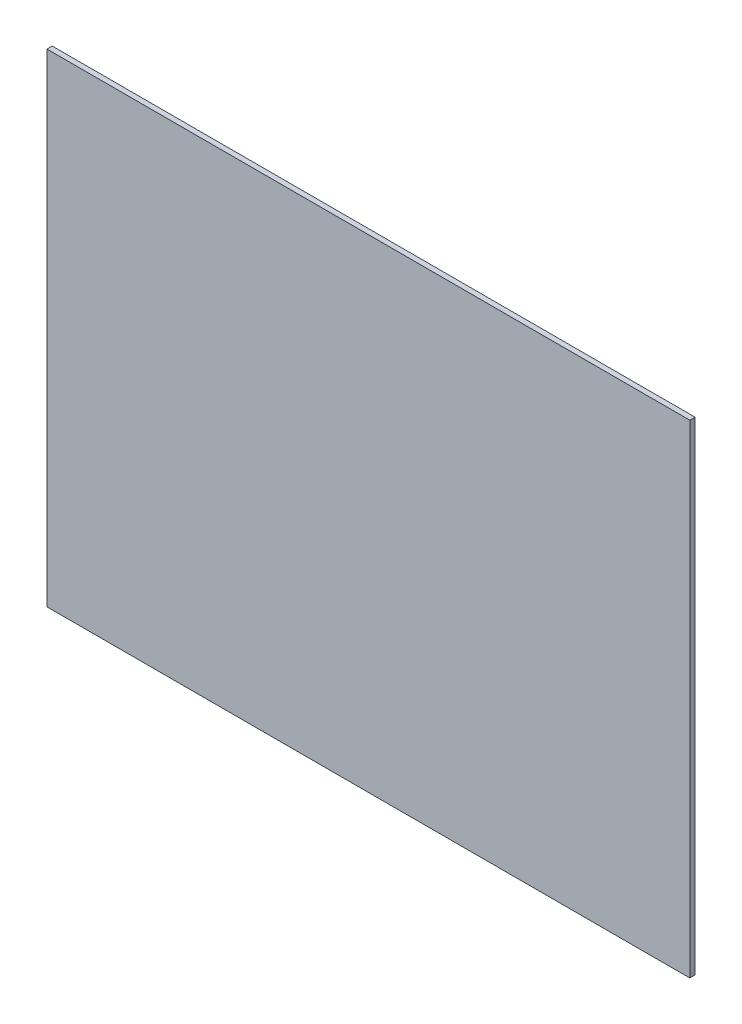
SolidWorks part; units mm, degrees
ref_plane "Спереди" through (0, 0, 0) normal (0, 0, 1) x (1, 0, 0)
ref_plane "Сверху" through (0, 0, 0) normal (0, 1, 0) x (1, 0, 0)
ref_plane "Справа" through (0, 0, 0) normal (1, 0, 0) x (0, 0, -1)
sketch "Sketch1" plane through (0, 0, 0) normal (0, 0, 1) x (1, 0, 0)
  line L0 (-110, 0) -> (-130, 0) construction
  line L5 (-130, 130) -> (360, 130)
  line L6 (-130, 130) -> (-130, -238.2)
  line L7 (-130, -238.2) -> (360, -238.2)
  line L8 (360, 130) -> (360, -238.2)
  line L9 (0, 110) -> (0, 130) construction
  line L10 (340, 0) -> (360, 0) construction
  line L11 (-120.2, -238.4) -> (-130.2, -238.4) construction
  circle A8 centre (230, 0) radius 110 construction
  circle A9 centre (0, 0) radius 110 construction
  circle A10 centre (230, 0) radius 110 construction
  circle A11 centre (0, 0) radius 110 construction
  dimension "D1" = 20
  dimension "D2" = 0.2
extrude "Extrude1" add sketch "Sketch1" along normal blind 4
equation "\"thickness\"=4"
equation "\"D1@Extrude1\"=\"thickness\""
